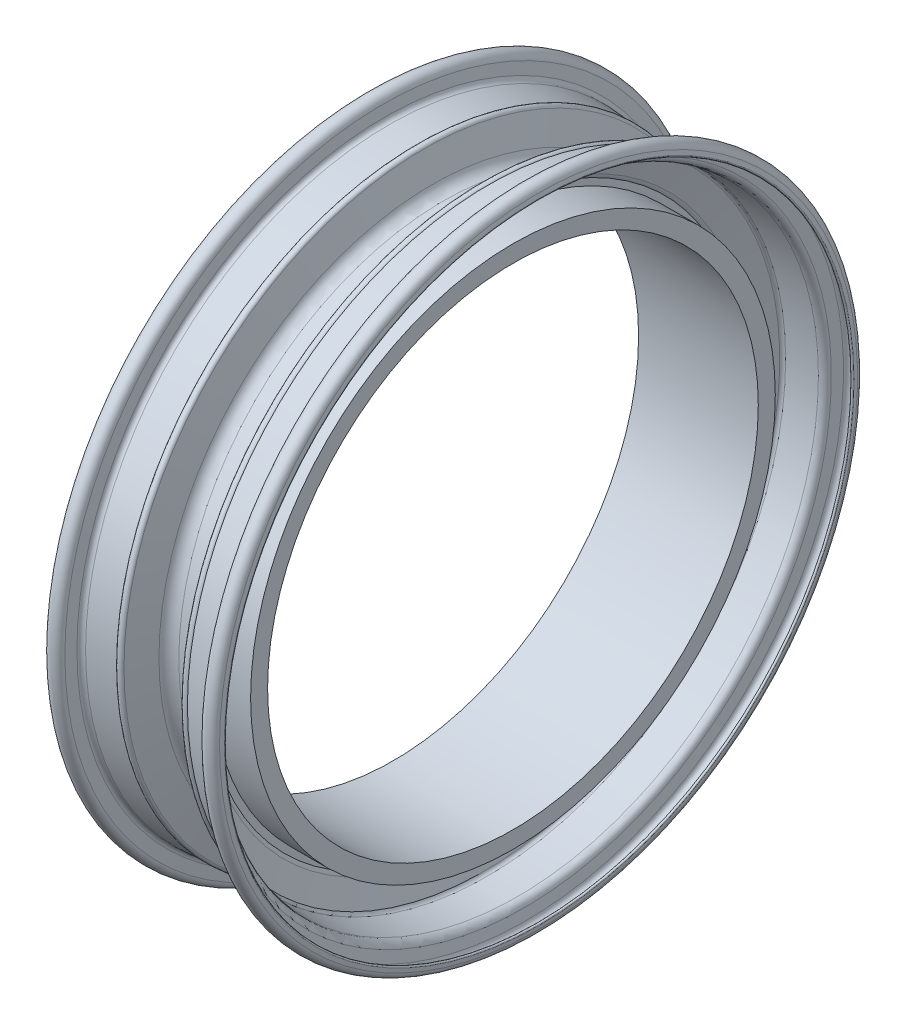
SolidWorks part; units mm, degrees
ref_plane "Front" through (0, 0, 0) normal (0, 0, 1) x (1, 0, 0)
ref_plane "Top" through (0, 0, 0) normal (0, 1, 0) x (1, 0, 0)
ref_plane "Right" through (0, 0, 0) normal (1, 0, 0) x (0, 0, -1)
other "Configuration Table"
sketch "Sketch1" plane through (0, 0, 0) normal (0, 0, 1) x (1, 0, 0)
  line L0 (-265.8191, 0) -> (333.5345, 0) construction
  line L1 (0, 472.207) -> (0, -397.2878) construction
  line L2 (-35.6874, 133.273) -> (-36, 131.5)
  line L3 (-29.1556, 133.0449) -> (-28.6763, 128.4854)
  line L4 (-26.8364, 126.7) -> (-14.7999, 125.8)
  line L5 (12.25, 125.247) -> (8.7728, 114.1099)
  line L6 (-12.25, 125.247) -> (-8.7728, 114.1099)
  line L7 (-25, 102.5) -> (25, 102.5)
  line L8 (26.8364, 126.7) -> (14.7999, 125.8)
  line L9 (29.1556, 133.0449) -> (28.6763, 128.4854)
  line L10 (-25, 102.5) -> (-25, 109.6)
  line L11 (-25, 109.6) -> (-9, 109.6)
  line L12 (35.6874, 133.273) -> (36, 131.5)
  line L13 (-32.4375, 136) -> (-18.5196, 136) construction
  line L14 (-5.8763, 126.3) -> (-13.6818, 126.3) construction
  line L15 (-4, 110.6) -> (4, 110.6)
  line L16 (34.7026, 133.0994) -> (35.0152, 131.3264)
  line L17 (30.1501, 132.9404) -> (29.6709, 128.3808)
  line L18 (26.911, 125.7028) -> (14.1794, 124.7508)
  line L19 (12.8006, 123.6553) -> (9.7273, 113.8118)
  line L20 (-4, 109.6) -> (4, 109.6)
  line L21 (-12.8006, 123.6553) -> (-9.7273, 113.8118)
  line L22 (-26.911, 125.7028) -> (-14.1794, 124.7508)
  line L23 (-30.1501, 132.9404) -> (-29.6709, 128.3808)
  line L24 (-34.7026, 133.0994) -> (-35.0152, 131.3264)
  line L25 (25, 102.5) -> (25, 109.6)
  line L26 (25, 109.6) -> (9, 109.6)
  line L27 (-9, 109.6) -> (-9, 113.1)
  line L28 (9, 109.6) -> (9, 113.1)
  line L29 (-4, 110.0098) -> (4, 110.0098)
  line L30 (-13.2046, 124.949) -> (-9.7273, 113.8118) construction
  line L31 (13.2046, 124.949) -> (9.7273, 113.8118) construction
  arc A0 (-29.1556, 133.0449) -> (-35.6874, 133.273) centre (-32.4375, 132.7) ccw
  arc A1 (12.25, 125.247) -> (14.7999, 125.8) centre (13.6818, 124.8) cw
  arc A2 (-12.25, 125.247) -> (-14.7999, 125.8) centre (-13.6818, 124.8) ccw
  arc A3 (29.1556, 133.0449) -> (35.6874, 133.273) centre (32.4375, 132.7) cw
  arc A4 (-28.6763, 128.4854) -> (-26.8364, 126.7) centre (-26.6873, 128.6944) ccw
  arc A5 (28.6763, 128.4854) -> (26.8364, 126.7) centre (26.6873, 128.6944) cw
  arc A6 (8.7728, 114.1099) -> (4, 110.6) centre (4, 115.6) cw
  arc A7 (-8.7728, 114.1099) -> (-4, 110.6) centre (-4, 115.6) ccw
  arc A8 (30.1501, 132.9404) -> (34.7026, 133.0994) centre (32.4375, 132.7) cw
  arc A9 (29.6709, 128.3808) -> (26.911, 125.7028) centre (26.6873, 128.6944) cw
  arc A11 (9.7273, 113.8118) -> (4, 109.6) centre (4, 115.6) cw
  arc A12 (-9.7273, 113.8118) -> (-4, 109.6) centre (-4, 115.6) ccw
  arc A14 (-29.6709, 128.3808) -> (-26.911, 125.7028) centre (-26.6873, 128.6944) ccw
  arc A15 (-30.1501, 132.9404) -> (-34.7026, 133.0994) centre (-32.4375, 132.7) ccw
  arc A16 (-36, 131.5) -> (-35.0152, 131.3264) centre (-35.5076, 131.4132) ccw
  arc A17 (36, 131.5) -> (35.0152, 131.3264) centre (35.5076, 131.4132) cw
  arc A18 (-9, 113.1) -> (-4, 110.0098) centre (-4, 115.6) ccw
  arc A19 (9, 113.1) -> (4, 110.0098) centre (4, 115.6) cw
  arc A20 (-13.2046, 124.949) -> (-14.1794, 124.7508) centre (-13.6818, 124.8) ccw construction
  arc A21 (13.2046, 124.949) -> (14.1794, 124.7508) centre (13.6818, 124.8) cw construction
  arc A22 (-14.1794, 124.7508) -> (-12.8006, 123.6553) centre (-14.2962, 123.1884) cw
  arc A23 (14.1794, 124.7508) -> (12.8006, 123.6553) centre (14.2962, 123.1884) ccw
  point P61 (7.6769, 110.6)
  point P64 (-7.6769, 110.6)
  dimension "D3" = 272
  dimension "D7" = 9.3
  dimension "D13" = 3.3
  dimension "D15" = 5
  dimension "D17" = 84
  dimension "D8" = 1.5
  dimension "D18" = 2
  dimension "D1" = 7.1
  dimension "D2" = 205
  dimension "D4" = 72
  dimension "D5" = 50
  dimension "D6" = 15.7
  dimension "D9" = 4.5
  dimension "D10" = 24.5
  dimension "D11" = 8
  dimension "D12" = 1
  dimension "D14" = 100
  dimension "D16" = 0.5
  dimension "D19" = 18
  dimension "3" = 3.5
revolve "Revolve1" add sketch "Sketch1" angle 360 about L0 region at (0, 106.1445, 0)
revolve "Revolve2" add sketch "Sketch1<4>" angle 360 about L0 region at (-32.3491, 135.2328, 0) region at (-8.8166, 112.6917, 0)
sketch "Sketch1<4>" plane through (0, 0, 0) normal (0, 0, 1) x (1, 0, 0) same geometry as "Sketch1"
